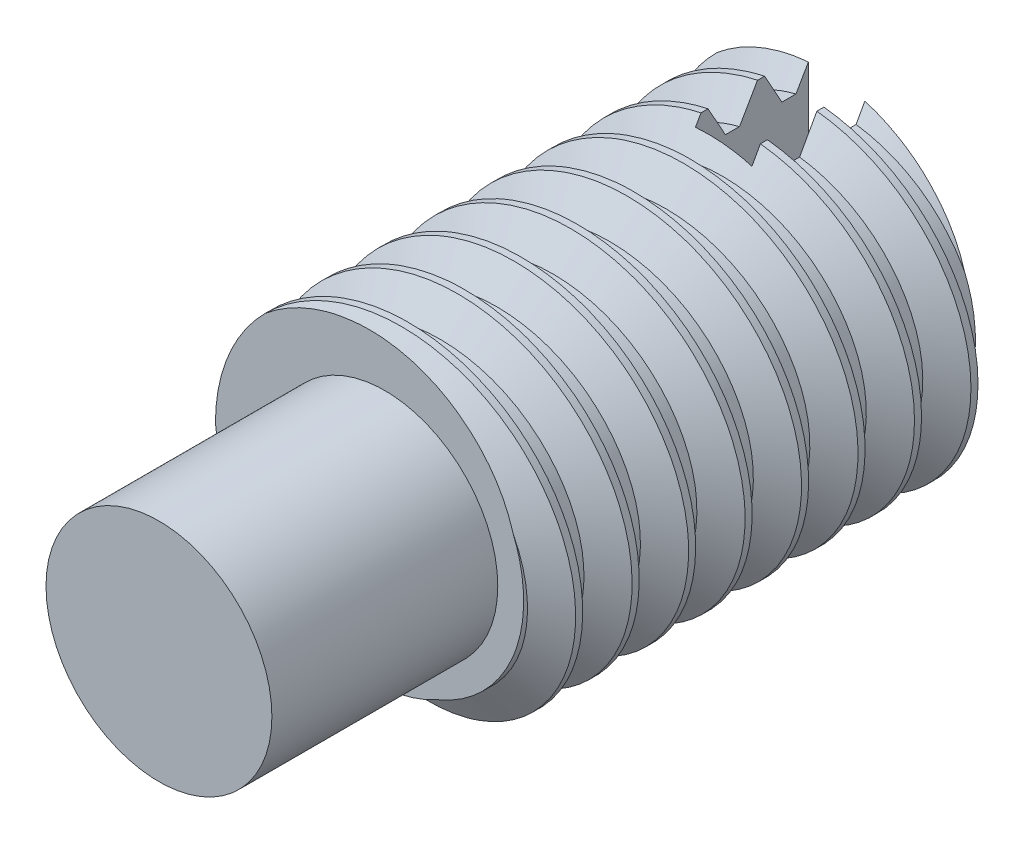
SolidWorks part; units mm, degrees
ref_plane "Front Plane" through (0, 0, 0) normal (0, 0, 1) x (1, 0, 0)
ref_plane "Top Plane" through (0, 0, 0) normal (0, 1, 0) x (1, 0, 0)
ref_plane "Right Plane" through (0, 0, 0) normal (1, 0, 0) x (0, 0, -1)
sketch "Sketch1" plane through (0, 0, 0) normal (0, 0, 1) x (1, 0, 0)
  circle A0 centre (0, 0) radius 3
  circle A1 centre (0, 0) radius 2
  dimension "D1" = 6
  dimension "D2" = 4
extrude "Boss-Extrude1" add sketch "Sketch1" along normal blind 12 contours A1 region at (0, 0, 0)
extrude "Boss-Extrude2" add sketch "Sketch1<3>" along normal blind 8
sketch "Sketch1<3>" plane through (0, 0, 0) normal (0, 0, 1) x (1, 0, 0) same geometry as "Sketch1"
sketch "Sketch2" plane through (0, 0, 0) normal (0, 0, -1) x (-1, 0, 0)
  line L1 (-0.5, 3.3461) -> (0.5, 3.3461)
  line L2 (-0.5, 3.3461) -> (-0.5, -3.3461)
  line L3 (-0.5, -3.3461) -> (0.5, -3.3461)
  line L4 (0.5, 3.3461) -> (0.5, -3.3461)
  line L5 (-0.5, 3.3461) -> (0.5, -3.3461) construction
  line L6 (-0.5, -3.3461) -> (0.5, 3.3461) construction
  point P0 (0, 0)
  dimension "D1" = 1
extrude "Cut-Extrude1" cut sketch "Sketch2" against normal blind 2
thread "Thread1" pitch 1 method cut profile "Thread Profile1" start angle 0, offset 1, length 10, pitch 1, diameter 6
ref_plane "Plane1" through (-3, 0, 9) normal (0, -1, 0) x (-1, 0, 0)
sketch "Thread Profile1" plane through (-3, 0, 9) normal (0, -1, 0) x (-1, 0, 0)
  line L0 (0, 0) -> (0, 1) construction
  line L11 (0, 0) -> (0, 0.875)
  line L12 (0, 0.875) -> (-0.5413, 0.5625)
  line L13 (-0.5413, 0.5625) -> (-0.5413, 0.3125)
  line L15 (-0.5413, 0.3125) -> (0, 0)
  line L17 (-0.5413, 0.4375) -> (0, 0.4375) construction
  point P2 (0, 0)
  dimension "Pitch" = 1
  dimension "Profile_Angle" = 60
  dimension "Profile_Land" = 0.25
  dimension "Profile_Height" = 0.5413
